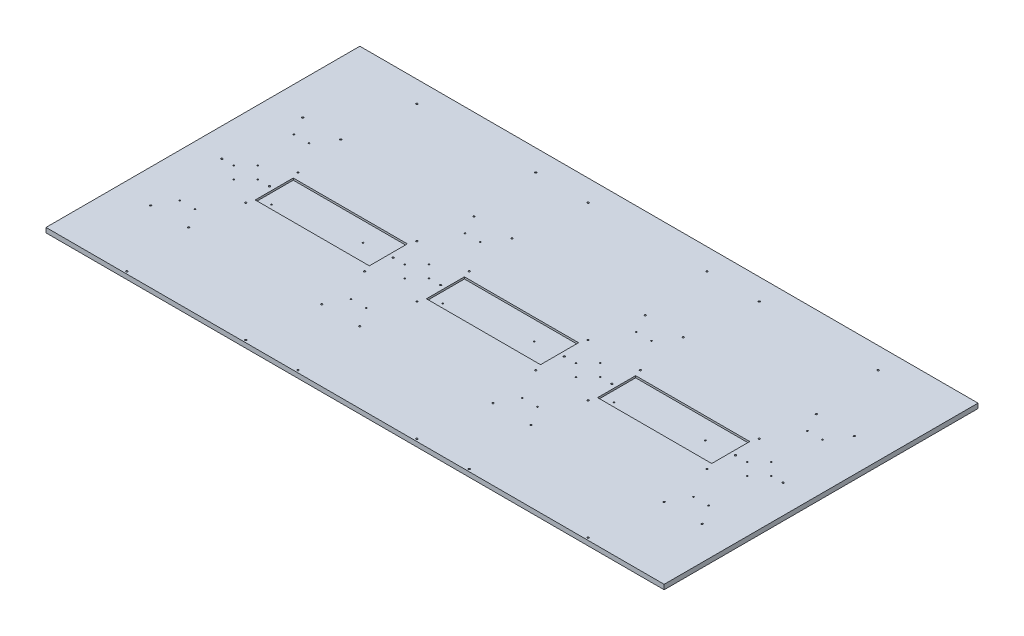
SolidWorks part; units mm, degrees
ref_plane "Front" through (0, 0, 0) normal (0, 0, 1) x (1, 0, 0)
ref_plane "Top" through (0, 0, 0) normal (0, 1, 0) x (1, 0, 0)
ref_plane "Right" through (0, 0, 0) normal (1, 0, 0) x (0, 0, -1)
sketch "Sketch1" plane through (0, 0, 0) normal (0, 1, 0) x (1, 0, 0)
  line L1 (0, 0) -> (800.1, 0)
  line L2 (0, 0) -> (0, 419.1)
  line L3 (0, 419.1) -> (800.1, 419.1)
  line L4 (800.1, 0) -> (800.1, 419.1)
  dimension "D1" = 419.1
  dimension "D2" = 800.1
extrude "Boss-Extrude1" add sketch "Sketch1" along normal blind 6.35
sketch "Sketch2" plane through (0, 6.35, 0) normal (0, 1, 0) x (1, 0, 0)
  line L0 (0, 0) -> (800.1, 0) construction
  line L1 (0, 419.1) -> (25.4, 419.1)
  line L2 (0, 419.1) -> (0, 0)
  line L3 (0, 0) -> (25.4, 0)
  line L4 (25.4, 419.1) -> (25.4, 0)
  line L5 (88.9, 165.1) -> (254, 165.1)
  line L6 (25.4, 419.1) -> (88.9, 419.1)
  line L7 (25.4, 419.1) -> (25.4, 0)
  line L8 (25.4, 0) -> (88.9, 0)
  line L9 (88.9, 419.1) -> (88.9, 0)
  line L10 (88.9, 0) -> (254, 0)
  line L11 (88.9, 0) -> (88.9, 165.1)
  line L12 (88.9, 165.1) -> (254, 165.1)
  line L13 (254, 0) -> (254, 165.1)
  line L14 (88.9, 165.1) -> (88.9, 228.6)
  line L15 (254, 165.1) -> (254, 228.6)
  line L16 (88.9, 228.6) -> (254, 228.6)
  line L17 (88.9, 228.6) -> (254, 228.6)
  line L18 (88.9, 228.6) -> (88.9, 393.7)
  line L19 (254, 228.6) -> (254, 393.7)
  line L20 (88.9, 393.7) -> (254, 393.7)
  line L21 (317.5, 419.1) -> (317.5, 0)
  line L22 (254, 419.1) -> (254, 0)
  line L23 (254, 419.1) -> (317.5, 419.1)
  line L24 (254, 0) -> (317.5, 0)
  line L25 (317.5, 228.6) -> (482.6, 228.6)
  line L26 (317.5, 228.6) -> (317.5, 393.7)
  line L27 (317.5, 393.7) -> (482.6, 393.7)
  line L28 (482.6, 228.6) -> (482.6, 393.7)
  line L29 (317.5, 165.1) -> (482.6, 165.1)
  line L30 (317.5, 165.1) -> (317.5, 228.6)
  line L31 (317.5, 228.6) -> (482.6, 228.6)
  line L32 (482.6, 165.1) -> (482.6, 228.6)
  line L33 (317.5, 0) -> (317.5, 165.1)
  line L34 (317.5, 0) -> (482.6, 0)
  line L35 (482.6, 0) -> (482.6, 165.1)
  line L36 (317.5, 165.1) -> (482.6, 165.1)
  line L37 (546.1, 419.1) -> (546.1, 0)
  line L38 (482.6, 419.1) -> (482.6, 0)
  line L39 (482.6, 419.1) -> (546.1, 419.1)
  line L40 (482.6, 0) -> (546.1, 0)
  line L41 (546.1, 228.6) -> (711.2, 228.6)
  line L42 (546.1, 228.6) -> (546.1, 393.7)
  line L43 (546.1, 393.7) -> (711.2, 393.7)
  line L44 (711.2, 228.6) -> (711.2, 393.7)
  line L45 (546.1, 165.1) -> (711.2, 165.1)
  line L46 (546.1, 165.1) -> (546.1, 228.6)
  line L47 (546.1, 228.6) -> (711.2, 228.6)
  line L48 (711.2, 165.1) -> (711.2, 228.6)
  line L49 (546.1, 0) -> (546.1, 165.1)
  line L50 (546.1, 0) -> (711.2, 0)
  line L51 (711.2, 0) -> (711.2, 165.1)
  line L52 (546.1, 165.1) -> (711.2, 165.1)
  line L53 (800.1, 419.1) -> (0, 419.1) construction
  line L54 (711.2, 0) -> (774.7, 0)
  line L55 (711.2, 0) -> (711.2, 419.1)
  line L56 (711.2, 419.1) -> (774.7, 419.1)
  line L57 (774.7, 0) -> (774.7, 419.1)
  line L58 (254, 196.85) -> (25.4, 196.85) construction
  line L59 (107.95, 228.6) -> (234.95, 228.6)
  line L60 (107.95, 228.6) -> (107.95, 368.3)
  line L61 (107.95, 368.3) -> (234.95, 368.3)
  line L62 (234.95, 228.6) -> (234.95, 368.3)
  line L63 (107.95, 25.4) -> (234.95, 25.4)
  line L64 (234.95, 165.1) -> (234.95, 25.4)
  line L65 (107.95, 165.1) -> (234.95, 165.1)
  line L66 (107.95, 165.1) -> (107.95, 25.4)
  line L67 (336.55, 228.6) -> (336.55, 368.3)
  line L68 (336.55, 228.6) -> (463.55, 228.6)
  line L69 (463.55, 228.6) -> (463.55, 368.3)
  line L70 (336.55, 368.3) -> (463.55, 368.3)
  line L71 (336.55, 25.4) -> (463.55, 25.4)
  line L72 (463.55, 165.1) -> (463.55, 25.4)
  line L73 (336.55, 165.1) -> (463.55, 165.1)
  line L74 (336.55, 165.1) -> (336.55, 25.4)
  line L75 (565.15, 228.6) -> (565.15, 368.3)
  line L76 (565.15, 228.6) -> (692.15, 228.6)
  line L77 (692.15, 228.6) -> (692.15, 368.3)
  line L78 (565.15, 368.3) -> (692.15, 368.3)
  line L79 (565.15, 25.4) -> (692.15, 25.4)
  line L80 (692.15, 165.1) -> (692.15, 25.4)
  line L81 (565.15, 165.1) -> (692.15, 165.1)
  line L82 (565.15, 165.1) -> (565.15, 25.4)
  dimension "D1" = 25.4
  dimension "D2" = 63.5
  dimension "D3" = 165.1
  dimension "D4" = 165.1
  dimension "D5" = 63.5
  dimension "D6" = 165.1
  dimension "D8" = 63.5
  dimension "D9" = 127
  dimension "D10" = 19.05
  dimension "D11" = 25.4
  dimension "D7" = 3
  dimension "D12" = 3
sketch "Sketch6" plane through (0, 6.35, 0) normal (0, 1, 0) x (1, 0, 0)
  line L0 (0, 419.1) -> (0, 0)
  line L1 (0, 419.1) -> (-12.7, 419.1)
  line L2 (0, 0) -> (-12.7, 0)
  line L3 (-12.7, 419.1) -> (-12.7, 0)
  line L4 (800.1, 419.1) -> (800.1, 0)
  line L5 (800.1, 419.1) -> (812.8, 419.1)
  line L6 (800.1, 0) -> (812.8, 0)
  line L7 (812.8, 419.1) -> (812.8, 0)
  dimension "D1" = 12.7
  dimension "D2" = 12.7
extrude "Boss-Extrude2" add sketch "Sketch6" against normal blind 6.35
sketch "Sketch4" plane through (0, 6.35, 0) normal (0, 1, 0) x (1, 0, 0)
  line L0 (88.9, 393.7) -> (254, 393.7) construction
  line L1 (88.9, 419.1) -> (88.9, 0) construction
  line L2 (88.9, 393.7) -> (254, 228.6) construction
  line L3 (254, 228.6) -> (254, 393.7) construction
  line L4 (254, 393.7) -> (88.9, 228.6) construction
  line L5 (254, 311.15) -> (101.6, 311.15) construction
  circle A0 centre (92.075, 390.525) radius 1.1303
  circle A1 centre (250.825, 231.775) radius 1.1303
  circle A2 centre (250.825, 390.525) radius 1.1303
  circle A3 centre (92.075, 231.775) radius 1.1303
  circle A4 centre (320.675, 390.525) radius 1.1303
  circle A5 centre (320.675, 231.775) radius 1.1303
  circle A6 centre (479.425, 231.775) radius 1.1303
  circle A7 centre (479.425, 390.525) radius 1.1303
  circle A8 centre (549.275, 390.525) radius 1.1303
  circle A9 centre (549.275, 231.775) radius 1.1303
  circle A10 centre (708.025, 231.775) radius 1.1303
  circle A11 centre (708.025, 390.525) radius 1.1303
  circle A12 centre (320.675, 161.925) radius 1.1303
  circle A13 centre (320.675, 3.175) radius 1.1303
  circle A14 centre (479.425, 3.175) radius 1.1303
  circle A15 centre (479.425, 161.925) radius 1.1303
  circle A16 centre (549.275, 161.925) radius 1.1303
  circle A17 centre (549.275, 3.175) radius 1.1303
  circle A18 centre (708.025, 3.175) radius 1.1303
  circle A19 centre (708.025, 161.925) radius 1.1303
  circle A20 centre (92.075, 161.925) radius 1.1303
  circle A21 centre (92.075, 3.175) radius 1.1303
  circle A22 centre (250.825, 3.175) radius 1.1303
  circle A23 centre (250.825, 161.925) radius 1.1303
  dimension "D1" = 2.2606
  dimension "D2" = 3.175
  dimension "D3" = 3.175
  dimension "D4" = 3
  dimension "D5" = 2
extrude "Cut-Extrude1" cut sketch "Sketch4" against normal through all both and the other way through all
sketch "Sketch5" plane through (0, 6.35, 0) normal (0, 1, 0) x (1, 0, 0)
  line L0 (57.15, 0) -> (57.15, 419.1) construction
  line L1 (25.4, 0) -> (88.9, 0) construction
  line L2 (25.4, 419.1) -> (88.9, 419.1) construction
  line L3 (88.9, 228.6) -> (88.9, 165.1) construction
  line L4 (88.9, 165.1) -> (26.9154, 196.85) construction
  line L5 (26.9154, 196.85) -> (88.9, 196.85) construction
  line L6 (88.9, 165.1) -> (254, 165.1) construction
  line L8 (88.9, 228.6) -> (254, 228.6) construction
  circle A0 centre (82.55, 95.25) radius 1.1303
  circle A1 centre (31.75, 95.25) radius 1.1303
  circle A2 centre (82.55, 298.45) radius 1.1303
  circle A3 centre (31.75, 298.45) radius 1.1303
  circle A4 centre (88.9, 196.85) radius 1.1303
  circle A5 centre (25.4, 196.85) radius 1.1303
  circle A6 centre (254, 196.85) radius 1.1303
  circle A7 centre (317.5, 196.85) radius 1.1303
  circle A8 centre (260.35, 95.25) radius 1.1303
  circle A9 centre (311.15, 95.25) radius 1.1303
  circle A10 centre (260.35, 298.45) radius 1.1303
  circle A11 centre (311.15, 298.45) radius 1.1303
  circle A12 centre (482.6, 196.85) radius 1.1303
  circle A13 centre (546.1, 196.85) radius 1.1303
  circle A14 centre (488.95, 95.25) radius 1.1303
  circle A15 centre (539.75, 95.25) radius 1.1303
  circle A16 centre (488.95, 298.45) radius 1.1303
  circle A17 centre (539.75, 298.45) radius 1.1303
  circle A18 centre (711.2, 196.85) radius 1.1303
  circle A19 centre (774.7, 196.85) radius 1.1303
  circle A20 centre (717.55, 95.25) radius 1.1303
  circle A21 centre (768.35, 95.25) radius 1.1303
  circle A22 centre (717.55, 298.45) radius 1.1303
  circle A23 centre (768.35, 298.45) radius 1.1303
  point P13 (57.15, 209.55)
  dimension "D1" = 2.2606
  dimension "D2" = 25.4
  dimension "D3" = 101.6
  dimension "D4" = 2.2606
  dimension "D5" = 31.75
  dimension "D6" = 31.75
  dimension "D7" = 2.2606
  dimension "D8" = 31.75
  dimension "D9" = 31.75
  dimension "D10" = 4
extrude "Cut-Extrude2" cut sketch "Sketch5" against normal through all
sketch "Sketch7" plane through (0, 6.35, 0) normal (0, 1, 0) x (1, 0, 0)
  line L0 (95.25, 196.85) -> (247.65, 196.85) construction
  line L1 (95.25, 222.25) -> (247.65, 222.25)
  line L2 (95.25, 222.25) -> (95.25, 171.45)
  line L3 (95.25, 171.45) -> (247.65, 171.45)
  line L4 (247.65, 222.25) -> (247.65, 171.45)
  line L5 (247.65, 196.85) -> (171.45, 222.25) construction
  line L6 (171.45, 222.25) -> (171.45, 171.45) construction
  line L7 (88.9, 419.1) -> (88.9, 0) construction
  line L8 (88.9, 228.6) -> (254, 228.6) construction
  line L9 (323.85, 222.25) -> (323.85, 171.45)
  line L10 (323.85, 222.25) -> (476.25, 222.25)
  line L11 (476.25, 222.25) -> (476.25, 171.45)
  line L12 (323.85, 171.45) -> (476.25, 171.45)
  line L13 (552.45, 222.25) -> (552.45, 171.45)
  line L14 (552.45, 222.25) -> (704.85, 222.25)
  line L15 (704.85, 222.25) -> (704.85, 171.45)
  line L16 (552.45, 171.45) -> (704.85, 171.45)
  dimension "D1" = 152.4
  dimension "D2" = 50.8
  dimension "D3" = 82.55
  dimension "D4" = 31.75
  dimension "D5" = 3
extrude "Cut-Extrude3" cut sketch "Sketch7" against normal blind 2.54
sketch "Sketch8" plane through (0, 3.81, 0) normal (0, 1, 0) x (1, 0, 0)
  line L0 (98.933, 196.85) -> (243.967, 196.85) construction
  line L1 (98.933, 174.625) -> (243.967, 174.625)
  line L2 (98.933, 174.625) -> (98.933, 219.075)
  line L3 (98.933, 219.075) -> (243.967, 219.075)
  line L4 (243.967, 174.625) -> (243.967, 219.075)
  line L5 (243.967, 196.85) -> (171.45, 174.625) construction
  line L6 (171.45, 174.625) -> (171.45, 219.075) construction
  line L7 (95.25, 222.25) -> (95.25, 171.45) construction
  line L8 (95.25, 171.45) -> (247.65, 171.45) construction
  circle A0 centre (109.1689, 179.451) radius 0.889
  circle A1 centre (214.249, 196.469) radius 0.889
  circle A2 centre (442.849, 196.469) radius 0.889
  circle A3 centre (337.7689, 179.451) radius 0.889
  circle A4 centre (671.449, 196.469) radius 0.889
  circle A5 centre (566.3689, 179.451) radius 0.889
  dimension "D5" = 1.778
  dimension "D6" = 4.826
  dimension "D7" = 10.2359
  dimension "D8" = 1.778
  dimension "D9" = 115.316
  dimension "D10" = 21.844
  dimension "D1" = 44.45
  dimension "D2" = 145.034
  dimension "D3" = 76.2
  dimension "D4" = 25.4
  dimension "D11" = 3
extrude "Cut-Extrude5" cut sketch "Sketch8" against normal through all contours A3 | A5 | A4 | A1 | A0 | A2 region at (337.7689, 3.81, -179.451) region at (671.449, 3.81, -196.469) region at (566.3689, 3.81, -179.451)
sketch "Sketch9" plane through (0, 6.35, 0) normal (0, 1, 0) x (1, 0, 0)
  line L0 (25.4, 196.85) -> (88.9, 196.85) construction
  line L1 (88.9, 419.1) -> (88.9, 0) construction
  line L2 (254, 196.85) -> (25.4, 196.85) construction
  circle A0 centre (40.9856, 196.85) radius 0.889
  circle A1 centre (57.15, 213.0144) radius 0.889
  circle A2 centre (73.3144, 196.85) radius 0.889
  circle A3 centre (57.15, 180.6856) radius 0.889
  circle A4 centre (269.5856, 196.85) radius 0.889
  circle A5 centre (285.75, 213.0144) radius 0.889
  circle A6 centre (301.9144, 196.85) radius 0.889
  circle A7 centre (285.75, 180.6856) radius 0.889
  circle A8 centre (498.1856, 196.85) radius 0.889
  circle A9 centre (514.35, 213.0144) radius 0.889
  circle A10 centre (530.5144, 196.85) radius 0.889
  circle A11 centre (514.35, 180.6856) radius 0.889
  circle A12 centre (726.7856, 196.85) radius 0.889
  circle A13 centre (742.95, 213.0144) radius 0.889
  circle A14 centre (759.1144, 196.85) radius 0.889
  circle A15 centre (742.95, 180.6856) radius 0.889
  point P10 (57.15, 196.85)
  point P19 (57.15, 196.85)
  dimension "D1" = 1.778
  dimension "D2" = 16.1644
  dimension "D3" = 4
  dimension "D4" = 4
extrude "Cut-Extrude6" cut sketch "Sketch9" against normal through all
sketch "Sketch10" plane through (0, 6.35, 0) normal (0, 1, 0) x (1, 0, 0)
  line L0 (31.75, 298.45) -> (79.1635, 298.45) construction
  line L1 (55.4568, 298.45) -> (55.4568, 273.9615) construction
  line L2 (25.4, 196.85) -> (88.9, 196.85) construction
  circle A0 centre (45.2968, 273.05) radius 0.889
  circle A1 centre (65.6168, 273.05) radius 0.889
  circle A2 centre (65.6168, 120.65) radius 0.889
  circle A3 centre (45.2968, 120.65) radius 0.889
  circle A4 centre (273.8968, 120.65) radius 0.889
  circle A5 centre (294.2168, 120.65) radius 0.889
  circle A6 centre (273.8968, 273.05) radius 0.889
  circle A7 centre (294.2168, 273.05) radius 0.889
  circle A8 centre (502.4968, 120.65) radius 0.889
  circle A9 centre (522.8168, 120.65) radius 0.889
  circle A10 centre (502.4968, 273.05) radius 0.889
  circle A11 centre (522.8168, 273.05) radius 0.889
  circle A12 centre (731.0968, 120.65) radius 0.889
  circle A13 centre (751.4168, 120.65) radius 0.889
  circle A14 centre (731.0968, 273.05) radius 0.889
  circle A15 centre (751.4168, 273.05) radius 0.889
  dimension "D1" = 25.4
  dimension "D3" = 1.778
  dimension "D2" = 10.16
  dimension "D4" = 4
extrude "Cut-Extrude7" cut sketch "Sketch10" against normal through all
